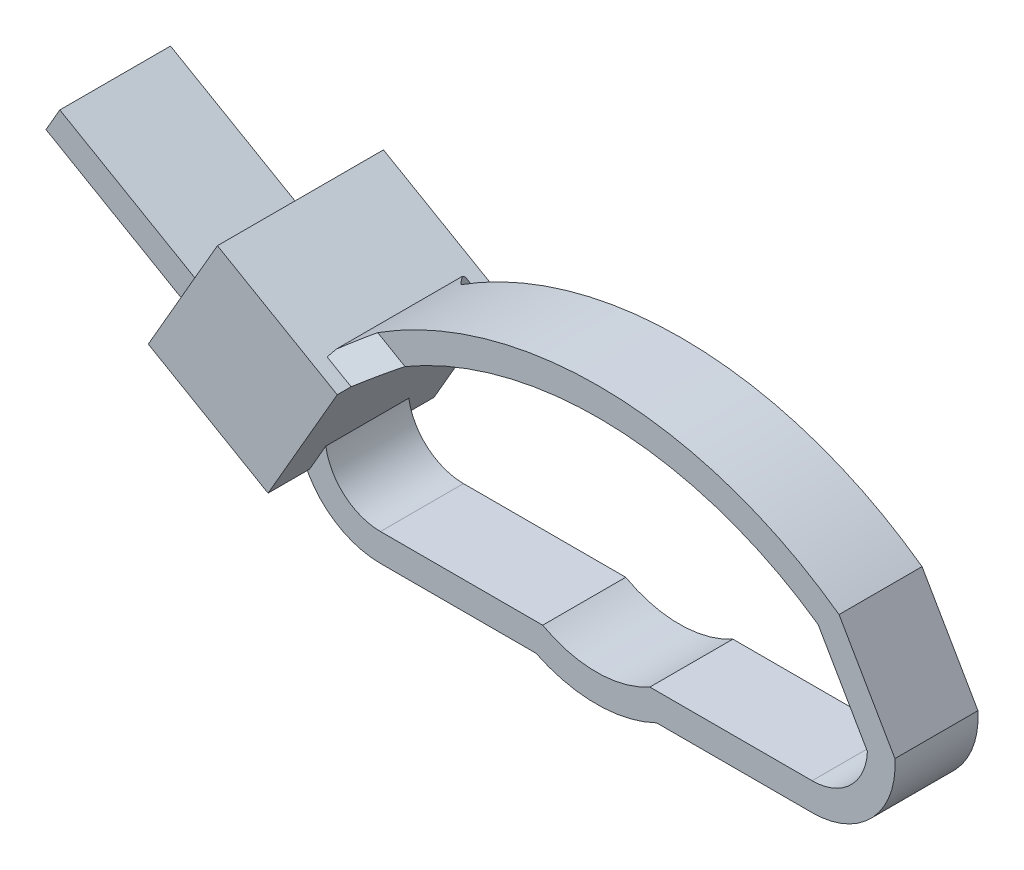
SolidWorks part; units mm, degrees
ref_plane "Front Plane" through (0, 0, 0) normal (0, 0, 1) x (1, 0, 0)
ref_plane "Top Plane" through (0, 0, 0) normal (0, 1, 0) x (1, 0, 0)
ref_plane "Right Plane" through (0, 0, 0) normal (1, 0, 0) x (0, 0, -1)
sketch "Sketch1" plane through (0, 0, 0) normal (0, 0, 1) x (1, 0, 0)
  line L0 (-7.8622, 12) -> (-3.7081, 12) construction
  line L1 (3.7081, 12) -> (8.0169, 12) construction
  line L2 (-2.1794, 6) -> (-7.8, 6)
  line L3 (-10.7988, 8.9137) -> (-8.6192, 12.6888)
  line L4 (8.7739, 12.6888) -> (10.794, 9.1899)
  line L5 (7.8, 6) -> (2.1794, 6)
  line L6 (-7.8622, 12) -> (-12.1923, 14.5)
  line L7 (-1.9365, 6) -> (-7.8, 6) construction
  line L8 (7.8, 6) -> (1.9365, 6) construction
  line L9 (-12.1923, 14.5) -> (-14.6923, 10.1699)
  line L10 (-14.6923, 10.1699) -> (-10.3622, 7.6699)
  line L11 (-10.3622, 7.6699) -> (-7.8622, 12)
  line L26 (-1.9365, 7) -> (-7.8, 7)
  line L27 (-9.7753, 8.6864) -> (-7.8622, 12)
  line L37 (8.0169, 12) -> (9.7982, 8.9147)
  line L38 (7.8, 7) -> (1.9365, 7)
  arc A0 (-10.7988, 8.9137) -> (-7.8, 6) centre (-7.8, 9) ccw
  arc A1 (-1.9365, 7) -> (1.9365, 7) centre (0, 10.5) ccw
  arc A2 (-1.9365, 7) -> (1.9365, 7) centre (0, 10.5) ccw
  arc A3 (-7.8622, 12) -> (8.0169, 12) centre (0.0774, 0.6445) cw
  arc A4 (3.7081, 12) -> (-3.7081, 12) centre (0, 10.5) ccw construction
  arc A5 (-8.6192, 12.6888) -> (8.7739, 12.6888) centre (0.0774, 0.6445) cw
  arc A6 (7.8, 6) -> (10.794, 9.1899) centre (7.8, 9) ccw
  arc A7 (-2.1794, 6) -> (2.1794, 6) centre (0, 10.5) ccw
  arc A9 (-2.4206, 6.125) -> (2.4206, 6.125) centre (0, 10.5) ccw construction
  arc A14 (-9.7753, 8.6864) -> (-7.8, 7) centre (-7.8, 9) ccw
  arc A19 (7.8, 7) -> (9.7982, 8.9147) centre (7.8, 9) ccw
  arc A20 (-1.9365, 7) -> (1.9365, 7) centre (0, 10.5) ccw
  dimension "D3" = 90
  dimension "D4" = 5
  dimension "D5" = 5
  dimension "D1" = 1
  dimension "D2" = 1
extrude "Boss-Extrude2" add sketch "Sketch1" along normal mid plane 3 contours A19 L38 A1 L26 A14 L11 L10 A0 L2 A7 L5 A6 L4 A5 L3 L6 A3 L37 region at (-4.9897, 6.2356, 0)
extrude "Boss-Extrude3" add sketch "Sketch1<5>" along normal mid plane 6 contours A0 L3 L6 L9 L10 | L3 A0 L10 L11 L6 region at (-9.4607, 10.1994, 0) region at (-11.6981, 11.2901, 0)
sketch "Sketch1<5>" plane through (0, 0, 0) normal (0, 0, 1) x (1, 0, 0) same geometry as "Sketch1"
sketch "Sketch2" plane through (-15.4229, 8.9044, 0) normal (-0.866, 0.5, 0) x (0, 0, 1)
  line L0 (2, 5.4612) -> (-2, 5.4612)
  line L1 (-2, 5.4612) -> (-2, 2.4612)
  line L2 (-2, 2.4612) -> (2, 2.4612)
  line L3 (2, 2.4612) -> (2, 5.4612)
  line L4 (-3, 6.4612) -> (-3, 1.4612)
  line L5 (-3, 1.4612) -> (3, 1.4612)
  line L6 (3, 1.4612) -> (3, 6.4612)
  line L7 (3, 6.4612) -> (-3, 6.4612)
  line L8 (-3, 6.4612) -> (-3, 1.4612)
  line L9 (-3, 1.4612) -> (3, 1.4612)
  line L10 (3, 1.4612) -> (3, 6.4612)
  line L11 (3, 6.4612) -> (-3, 6.4612)
  line L13 (2, 2.4612) -> (-2, 2.4612)
  line L14 (2, 2.4612) -> (2, 3.4612)
  line L15 (2, 3.4612) -> (-2, 3.4612)
  line L16 (-2, 2.4612) -> (-2, 3.4612)
  dimension "D3" = 1
  dimension "D1" = 0
  dimension "D2" = 1
extrude "Boss-Extrude4" add sketch "Sketch2" along normal blind 6 contours L3 L15 L1 L2 region at (-13.9423, 11.4689, 0)
extrude "Cut-Extrude1" cut sketch "Sketch2<3>" against normal blind 1 contours L15 L3 L0 L1 region at (-13.1923, 12.7679, 0)
sketch "Sketch2<3>" plane through (-15.4229, 8.9044, 0) normal (-0.866, 0.5, 0) x (0, 0, 1) same geometry as "Sketch2"
chamfer "Chamfer1" distance 1 angle 45 2 edges at (-8.2952, 12.25, -1.5) (-8.2952, 12.25, 1.5)
